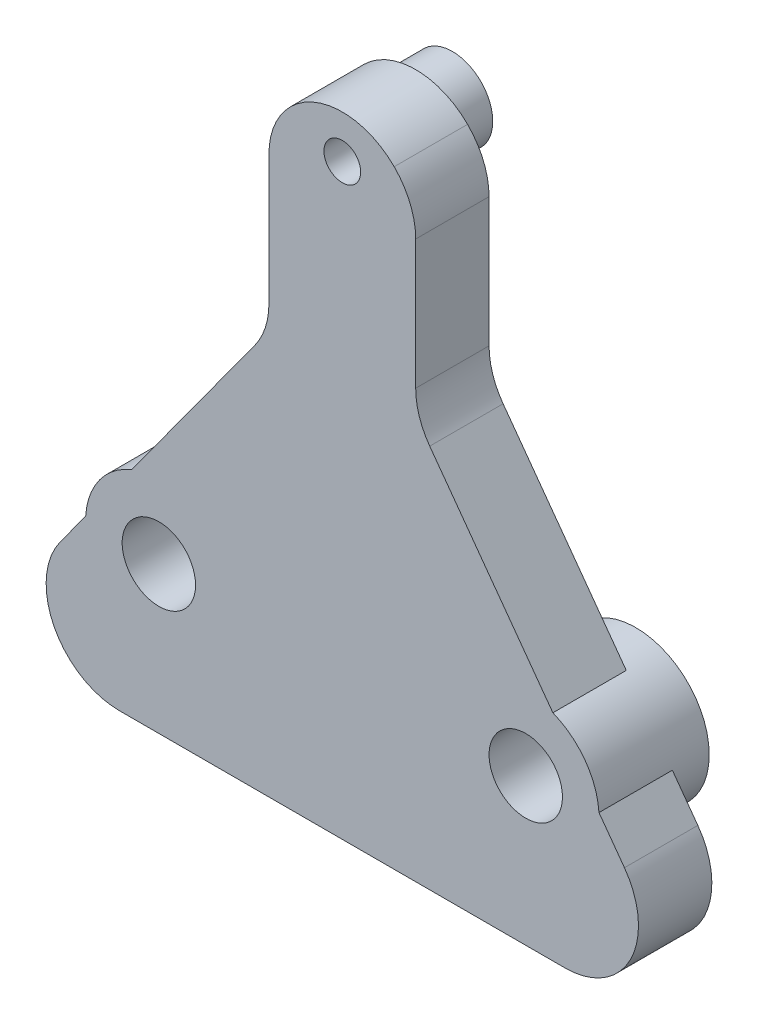
SolidWorks part; units mm, degrees
ref_plane "前视基准面" through (0, 0, 0) normal (0, 0, 1) x (1, 0, 0)
ref_plane "上视基准面" through (0, 0, 0) normal (0, 1, 0) x (1, 0, 0)
ref_plane "右视基准面" through (0, 0, 0) normal (1, 0, 0) x (0, 0, -1)
sketch "草图1" plane through (0, 0, 0) normal (0, 0, 1) x (1, 0, 0)
  line L0 (0, 18.2926) -> (0, -17.3298) construction
  line L3 (-10, -4) -> (10, -4)
  line L5 (-8.1099, 3.9151) -> (10, -4.8276) construction
  line L6 (-10, -4.8276) -> (8.1099, 3.9151) construction
  line L7 (-20.4077, 0) -> (10, 0) construction
  line L8 (-2, 7) -> (-2, 12)
  line L10 (2, 12) -> (2, 7)
  line L14 (-2, 12) -> (0, 14)
  line L19 (2, 12) -> (0, 14)
  line L25 (-2, 7) -> (-10, -4)
  line L26 (2, 7) -> (10, -4)
  circle A4 centre (-5, 0) radius 1
  circle A5 centre (5, 0) radius 1
  circle A6 centre (-5, 0) radius 5 construction
  circle A7 centre (5, 0) radius 5 construction
  circle A8 centre (0, 12) radius 0.5
  point P0 (0, 0)
  dimension "D4" = 2
  dimension "D5" = 5
  dimension "D6" = 10
  dimension "D9" = 1
  dimension "D2" = 4
extrude "凸台-拉伸1" add sketch "草图1" along normal blind 2
fillet "圆角1" radius 2 5 edges at (0, 14, 1) (2, 12, 1) (-2, 12, 1) (-2, 7, 1) (2, 7, 1)
fillet "圆角2" radius 2 2 edges at (10, -4, 1) (-10, -4, 1)
sketch "草图3" plane through (0, 0, 2) normal (0, 0, 1) x (1, 0, 0)
  circle A0 centre (0, 12) radius 1.1
  circle A1 centre (-5, 0) radius 2
  circle A2 centre (5, 0) radius 2
  circle A3 centre (-5, 0) radius 1
  circle A4 centre (5, 0) radius 1
  circle A5 centre (0, 12) radius 0.5
  dimension "D1" = 4
  dimension "D2" = 4
  dimension "D3" = 2.2
extrude "凸台-拉伸3" add sketch "草图3" against normal blind 3
